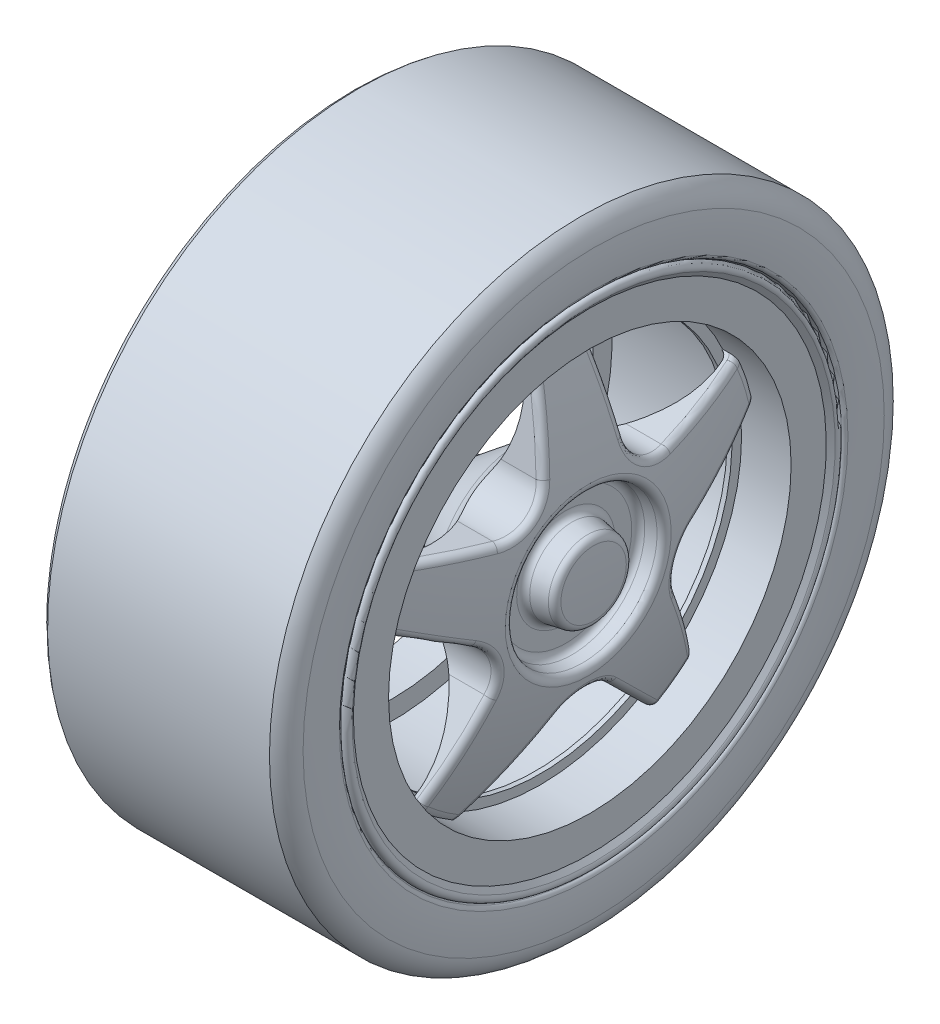
SolidWorks part; units mm, degrees
material "ABS"
ref_plane "Alzado" through (0, 0, 0) normal (0, 0, 1) x (1, 0, 0)
ref_plane "Planta" through (0, 0, 0) normal (0, 1, 0) x (1, 0, 0)
ref_plane "Vista lateral" through (0, 0, 0) normal (1, 0, 0) x (0, 0, -1)
sketch "Croquis1" plane through (0, 0, 0) normal (0, 0, 1) x (1, 0, 0)
  line L0 (-13, 26) -> (13, 26) construction
  line L1 (-13, 0) -> (13, 0) construction
  line L2 (-13, 0) -> (-13, 33) construction
  line L3 (-13, 33) -> (13, 33) construction
  line L4 (13, 0) -> (13, 33) construction
  line L5 (-12.2647, 25.9412) -> (-10.5, 25)
  line L6 (12.2647, 25.9412) -> (10.5, 25)
  line L7 (-10.5, 25) -> (10.5, 25)
  line L8 (0, 26) -> (0, 25) construction
  line L9 (12.8997, 25.1996) -> (12.5, 24.6678)
  line L10 (12.5, 24.6678) -> (12.5, 21)
  line L11 (12.5, 21) -> (8.8322, 21)
  line L12 (12.8574, 4) -> (10, 4.5)
  line L13 (10, 4.5) -> (10, 7.5)
  line L14 (10, 7.5) -> (12.4379, 7.9266)
  line L15 (-12.8997, 25.1996) -> (-12.5, 24.6678)
  line L16 (-12.5, 24.6678) -> (-12.5, 21)
  line L17 (-12.5, 21) -> (6.8322, 21)
  line L18 (13, 0) -> (-16, 0)
  line L19 (-16, 0) -> (-16, 4)
  line L20 (-16, 4) -> (0.8553, 6.9494)
  line L21 (13, 0) -> (15.4749, 0) construction
  line L22 (10, 6) -> (12.4749, 6) construction
  line L23 (-0.8188, 16.5163) -> (8.2297, 20.045) construction
  line L24 (6.8322, 21) -> (8.8322, 21)
  arc A0 (-12.8997, 25.1996) -> (-12.2647, 25.9412) centre (-12.5, 25.5) cw
  arc A1 (12.8997, 25.1996) -> (12.2647, 25.9412) centre (12.5, 25.5) ccw
  arc A2 (8.8322, 21) -> (9.1614, 20.4083) centre (6.8322, 19.5) cw
  arc A3 (9.1614, 20.4083) -> (12.4379, 7.9266) centre (-43.1704, 0) cw
  arc A4 (12.4379, 7.9266) -> (12.8574, 4) centre (-43.1704, 0) cw construction
  arc A5 (12.8574, 4) -> (13, 0) centre (-43.1704, 0) cw
  arc A6 (0.8553, 6.9494) -> (8.2297, 20.045) centre (-0.8188, 16.5163) ccw
  arc A7 (8.2297, 20.045) -> (6.8322, 21) centre (6.8322, 19.5) ccw
  dimension "D6" = 0.5
  dimension "D9" = 2.5
  dimension "D15" = 1
  dimension "D1" = 33
  dimension "D2" = 26
  dimension "D3" = 26
  dimension "D4" = 1
  dimension "D5" = 2
  dimension "D7" = 25
  dimension "D8" = 5
  dimension "D10" = 8
  dimension "D11" = 3
  dimension "D12" = 0.5
  dimension "D13" = 3
  dimension "D14" = 29
revolve "Revolución1" add sketch "Croquis1" angle 360 about L18 region at (0, 23.0694, 0)
revolve "Revolución2" add sketch "Croquis1<3>" angle 360 about L18 region at (1.3597, 4.9037, 0)
sketch "Croquis1<3>" plane through (0, 0, 0) normal (0, 0, 1) x (1, 0, 0) same geometry as "Croquis1"
sketch "Croquis2" plane through (0, 0, 0) normal (1, 0, 0) x (0, 0, -1)
  line L0 (-19.0325, 8.8749) -> (-8.789, 7.3126)
  line L1 (-2.4669, 21.4052) -> (-2.5592, 20.8435) construction
  line L2 (-19.5952, 8.9608) -> (-19.0325, 8.8749) construction
  line L3 (-2.5592, 20.8435) -> (-4.2387, 10.6185)
  circle A0 centre (0, 21) radius 2.5 construction
  circle A1 centre (0, 0) radius 21 construction
  circle A2 centre (19.9722, 6.4894) radius 2.5
  circle A3 centre (12.3435, -16.9894) radius 2.5
  circle A4 centre (-12.3435, -16.9894) radius 2.5
  circle A5 centre (-19.9722, 6.4894) radius 2.5 construction
  arc A6 (-8.789, 7.3126) -> (-4.2387, 10.6185) centre (-8.1858, 11.2669) ccw
  arc A7 (-4.2387, 10.6185) -> (-8.789, 7.3126) centre (-8.1858, 11.2669) ccw construction
  circle A8 centre (0, 0) radius 9.9266 construction
  circle A9 centre (0, 0) radius 7.9266 construction
  arc A10 (-19.0325, 8.8749) -> (-2.5592, 20.8435) centre (0, 0) cw
  point P16 (0, 0)
  dimension "D1" = 5
  dimension "D3" = 8
  dimension "D4" = 2
  dimension "D2" = 5
extrude "Cortar-Extruir1" cut sketch "Croquis2" along normal blind 29 contours A10 L0 A6 L3 region at (0, 13.2098, 9.5975)
ref_axis "Eje1" through (0.8553, 0, 0) along (-1, 0, 0)
pattern_circular "MatrizC1" count 5 over 360 about axis through (0.8553, 0, 0) along (-1, 0, 0) of "Cortar-Extruir1"
sketch "Croquis3" plane through (0, 0, 0) normal (0, 0, 1) x (1, 0, 0)
  line L0 (7.3322, 22.5) -> (7.3322, 19.5)
  line L1 (6.8322, 21) -> (-8.1678, 21)
  line L2 (6.8322, 21) -> (6.8322, 23)
  line L3 (6.8322, 23) -> (-8.1678, 23)
  line L4 (-8.1678, 21) -> (-8.1678, 23)
  line L5 (7.3322, 19.5) -> (6.8322, 19.5)
  line L6 (6.8322, 19.5) -> (6.8322, 21)
  line L7 (6.8322, 23) -> (7.3322, 23)
  line L8 (7.3322, 23) -> (7.3322, 22.5)
  arc A0 (6.8322, 23) -> (7.3322, 22.5) centre (6.8322, 22.5) cw construction
  dimension "D1" = 2
  dimension "D2" = 0.5
  dimension "D3" = 1.5
  dimension "D4" = 15
revolve "Cortar-Revolución1" cut sketch "Croquis3" angle 360 about axis through (0.8553, 0, 0) along (-1, 0, 0) region at (7.0822, 21.25, 0) region at (-0.6678, 22, 0)
sketch "Croquis4" plane through (0, 0, 0) normal (0, 0, 1) x (1, 0, 0)
  line L0 (12.5, 21) -> (7.3322, 21) construction
  line L1 (7.3322, 23) -> (6.8322, 23)
  line L2 (7.3322, 23) -> (7.3322, 20)
  line L3 (7.3322, 20) -> (6.8322, 20)
  line L4 (6.8322, 23) -> (6.8322, 21.5) construction
  line L5 (6.8322, 23) -> (5.3322, 23)
  line L6 (7.3322, 23) -> (-8.1678, 23) construction
  line L7 (6.8322, 21.5) -> (6.8322, 20)
  arc A0 (5.3322, 23) -> (6.8322, 21.5) centre (5.3322, 21.5) cw
  dimension "D1" = 1
  dimension "D2" = 0.5
revolve "Revolución3" add sketch "Croquis4" angle 360 about axis through (0.8553, 0, 0) along (-1, 0, 0)
fillet "Redondeo1" radius 0.75 28 edges at (12.1094, -3.5064, 9.3252) (10.7135, 1.5145, 15.7908) (10.7135, 8.0563, 13.6652) (12.1094, 7.7853, 6.2165) (10.7135, 15.4859, 3.4392) (10.7135, 15.4859, -3.4392) (12.1094, 8.318, -5.4832) (10.7135, 8.0563, -13.6652) (10.7135, 1.5145, -15.7908) (12.1094, -2.6445, -9.6053) (10.7135, -10.5069, -11.8848) (10.7135, -14.5499, -6.32) (12.1094, -9.9523, -0.4532) (10.7135, -14.5499, 6.32) (10.7135, -10.5069, 11.8848) (12.8574, 4, 0) (10, 4.5, 0) (10, 7.5, 0)
sketch "Croquis6" plane through (0, 0, 0) normal (0, 0, 1) x (1, 0, 0)
  line L0 (-16, 4) -> (-1, 4)
  line L1 (-1, 4) -> (5.1987, 8.8928)
  line L2 (-16, 4) -> (0.8553, 6.9494)
  arc A0 (0.8553, 6.9494) -> (5.1987, 8.8928) centre (-0.8188, 16.5163) ccw
  arc A1 (0.8553, 6.9494) -> (8.8934, 16.5163) centre (-0.8188, 16.5163) ccw construction
  dimension "D1" = 15
revolve "Cortar-Revolución4" cut sketch "Croquis6" angle 360 about axis through (0.8553, 0, 0) along (-1, 0, 0)
sketch "Croquis7" plane through (0, 0, 0) normal (0, 0, 1) x (1, 0, 0)
  line L0 (-13, 0) -> (-13, 33) construction
  line L1 (-12.2647, 25.9412) -> (-10.5, 25) construction
  line L2 (12.6381, 26.1403) -> (10.5, 25)
  line L3 (-10.5, 25) -> (10.5, 25)
  line L4 (13, 0) -> (13, 33) construction
  line L5 (0, 32.9) -> (0, 33) construction
  line L8 (-13, 33) -> (13, 33) construction
  line L9 (-12.6381, 26.1403) -> (-10.5, 25)
  arc A0 (-12.9, 26.5288) -> (-12.9, 30.316) centre (4.9782, 28.4224) cw
  arc A1 (-12.2647, 25.9412) -> (-12.8997, 25.1996) centre (-12.5, 25.5) ccw construction
  arc A2 (-9.8562, 32.9994) -> (9.8562, 32.9994) centre (0, 521.6534) ccw
  arc A3 (12.9, 30.316) -> (12.9, 26.5288) centre (-4.9782, 28.4224) cw
  arc A4 (12.9, 30.316) -> (9.8562, 32.9994) centre (9.9167, 30) ccw
  arc A5 (-12.9, 30.316) -> (-9.8562, 32.9994) centre (-9.9167, 30) cw
  arc A6 (-12.9, 26.5288) -> (-12.6381, 26.1403) centre (-12.4028, 26.5815) ccw
  arc A7 (12.9, 26.5288) -> (12.6381, 26.1403) centre (12.4028, 26.5815) cw
  arc A8 (12.8997, 25.1996) -> (12.2647, 25.9412) centre (12.5, 25.5) ccw construction
  dimension "D1" = 3
  dimension "D2" = 0.1
  dimension "D3" = 0.1
revolve "Revolución4" add sketch "Croquis7" angle 360 about L18
fillet "Redondeo2" radius 0.75 1 edges at (12.4379, 7.9266, 0)
sketch "Croquis8" plane through (-16, 0, 0) normal (-1, 0, 0) x (0, 0, 1)
  line L0 (-1.8, 2.0125) -> (-1.8, -2.0125)
  line L1 (1.8, -2.0125) -> (1.8, 2.0125)
  circle A0 centre (0, 0) radius 2.7 construction
  circle A1 centre (0, 0) radius 4 construction
  arc A2 (-1.8, 2.0125) -> (1.8, 2.0125) centre (0, 0) cw
  arc A3 (-1.8, -2.0125) -> (1.8, -2.0125) centre (0, 0) ccw
  dimension "D1" = 5.4
  dimension "D2" = 3.6
extrude "Cortar-Extruir2" cut sketch "Croquis8" against normal blind 10
sketch "Эскиз1" plane through (0, 0, 0) normal (1, 0, 0) x (0, 0, -1)
  circle A0 centre (0, 0) radius 32.5
  circle A1 centre (0, 0) radius 41.1363
extrude "Вырез-Вытянуть4" cut sketch "Эскиз1" along normal through all both and the other way through all contours A1 A0 region at (0, 0, 39.9728)
